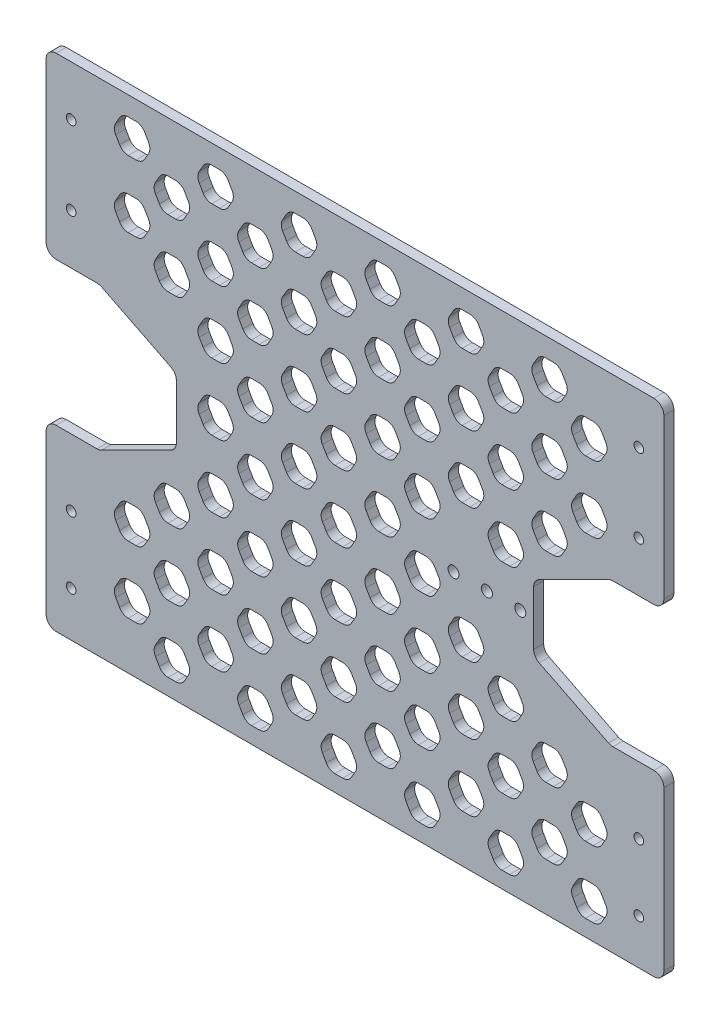
SolidWorks part; units mm, degrees
material "轻木"
ref_plane "前视基准面" through (0, 0, 0) normal (0, 0, 1) x (1, 0, 0)
ref_plane "上视基准面" through (0, 0, 0) normal (0, 1, 0) x (1, 0, 0)
ref_plane "右视基准面" through (0, 0, 0) normal (1, 0, 0) x (0, 0, -1)
other "Configuration Table"
sketch "草图2" plane through (0, 0, 0) normal (0, 0, 1) x (1, 0, 0)
  line L0 (-15, 79) -> (-15, 17.5) construction
  line L1 (-155.6985, 79) -> (0, 79) construction
  line L2 (-15, 285) -> (-15, -285) construction
  line L3 (-15, 17.5) -> (0, 17.5) construction
  line L4 (0, 285) -> (0, -285) construction
  line L5 (0, 17.5) -> (20, 7.5) construction
  line L6 (155, 7.5) -> (0, 7.5) construction
  line L8 (155, -7.5) -> (0, -7.5) construction
  line L9 (20, -7.5) -> (135, -7.5) construction
  line L11 (135, 7.5) -> (155, 17.5) construction
  line L12 (155, 285) -> (155, -285) construction
  line L13 (155, 17.5) -> (170, 17.5) construction
  line L14 (170, 285) -> (170, -285) construction
  line L15 (170, 17.5) -> (170, 79) construction
  line L16 (170, 79) -> (-15, 79) construction
  line L17 (20, 7.5) -> (20, -7.5) construction
  line L18 (137.7639, 8.882) -> (153.9443, 16.9721) construction
  line L19 (1.0557, 16.9721) -> (17.2361, 8.882) construction
  line L20 (-1000, 0) -> (49000, 0) construction
  line L21 (135, 7.5) -> (135, -7.5) construction
  line L22 (131, 9.9721) -> (131, -3.5) construction
  line L23 (24, -3.5) -> (131, -3.5) construction
  line L24 (24, 9.9721) -> (24, -3.5) construction
  line L25 (0.9443, 21.5) -> (24, 9.9721) construction
  line L26 (-11, 21.5) -> (0.9443, 21.5) construction
  line L27 (-11, 75) -> (-11, 21.5) construction
  line L28 (166, 75) -> (-11, 75) construction
  line L29 (166, 21.5) -> (166, 75) construction
  line L30 (154.0557, 21.5) -> (166, 21.5) construction
  line L31 (131, 9.9721) -> (154.0557, 21.5) construction
  line L32 (131, -9.9721) -> (154.0557, -21.5) construction
  line L33 (154.0557, -21.5) -> (166, -21.5) construction
  line L34 (166, -21.5) -> (166, -75) construction
  line L35 (166, -75) -> (-11, -75) construction
  line L36 (-11, -75) -> (-11, -21.5) construction
  line L37 (-11, -21.5) -> (0.9443, -21.5) construction
  line L38 (0.9443, -21.5) -> (24, -9.9721) construction
  line L39 (24, -9.9721) -> (24, 3.5) construction
  line L40 (24, 3.5) -> (131, 3.5) construction
  line L41 (131, -9.9721) -> (131, 3.5) construction
  line L42 (170, 75) -> (-15, 75)
  line L43 (-15, 75) -> (-15, 21.5)
  line L44 (-15, 21.5) -> (0.9443, 21.5)
  line L45 (0.9443, 21.5) -> (24, 9.9721)
  line L46 (24, 9.9721) -> (24, -9.9721)
  line L47 (24, -9.9721) -> (0.9443, -21.5)
  line L48 (0.9443, -21.5) -> (-15, -21.5)
  line L49 (-15, -21.5) -> (-15, -75)
  line L50 (-15, -75) -> (170, -75)
  line L51 (170, -75) -> (170, -21.5)
  line L52 (170, -21.5) -> (154.0557, -21.5)
  line L53 (154.0557, -21.5) -> (131, -9.9721)
  line L54 (131, -9.9721) -> (131, 9.9721)
  line L55 (131, 9.9721) -> (154.0557, 21.5)
  line L56 (154.0557, 21.5) -> (170, 21.5)
  line L57 (170, 21.5) -> (170, 75)
  dimension "D1" = 4
extrude "凸台-拉伸1" add sketch "草图2" along normal blind 3
fillet "圆角1" radius 3 16 edges at (131, 9.9721, 1.5) (131, -9.9721, 1.5) (154.0557, -21.5, 1.5) (170, -21.5, 1.5) (170, -75, 1.5) (-15, -75, 1.5) (-15, -21.5, 1.5) (0.9443, -21.5, 1.5) (24, -9.9721, 1.5) (24, 9.9721, 1.5) (0.9443, 21.5, 1.5) (-15, 21.5, 1.5) (-15, 75, 1.5) (154.0557, 21.5, 1.5) (170, 21.5, 1.5) (170, 75, 1.5)
sketch "草图3" plane through (0, 0, 3) normal (0, 0, 1) x (1, 0, 0)
  line L0 (-7.5, 86.2076) -> (-7.5, -86.6674) construction
  line L1 (162.5, 91.5716) -> (162.5, -92.3379) construction
  line L2 (170, 24.5) -> (170, 72) construction
  line L5 (-15, 72) -> (-15, 24.5) construction
  line L6 (-12, 21.5) -> (0.2361, 21.5) construction
  line L7 (167, 75) -> (-12, 75) construction
  line L8 (154.7639, 21.5) -> (167, 21.5) construction
  line L9 (167, -21.5) -> (154.7639, -21.5) construction
  line L11 (0.2361, -21.5) -> (-12, -21.5) construction
  circle A0 centre (-7.5, 60) radius 1.45
  circle A1 centre (162.5, 60) radius 1.45
  circle A2 centre (-7.5, -61.5) radius 1.45
  circle A3 centre (162.5, -61.5) radius 1.45
  circle A4 centre (-7.5, 36.5) radius 1.45
  circle A5 centre (162.5, 36.5) radius 1.45
  circle A6 centre (162.5, -41.5) radius 1.45
  circle A7 centre (-7.5, -41.5) radius 1.45
  dimension "D3" = 2.9
  dimension "D4" = 15
  dimension "D5" = 15
  dimension "D6" = 15
  dimension "D7" = 15
  dimension "D8" = 20
  dimension "D9" = 20
  dimension "D11" = 20
  dimension "D1" = 7.5
  dimension "D2" = 7.5
  dimension "D10" = 20
extrude "切除-拉伸1" cut sketch "草图3" against normal blind 10
sketch "草图4" plane through (0, 0, 0) normal (0, 0, -1) x (-1, 0, 0)
  circle A0 centre (-127, 0) radius 1.65 construction
  circle A1 centre (-127, 0) radius 1.65
  circle A2 centre (-107, 0) radius 1.65 construction
  circle A3 centre (-117, 0) radius 1.65 construction
  circle A4 centre (-107, 0) radius 1.65
  circle A5 centre (-117, 0) radius 1.65
extrude "切除-拉伸2" cut sketch "草图4" against normal through all
sketch "草图5" plane through (0, 0, 3) normal (0, 0, 1) x (1, 0, 0)
  line L1 (41.534, 64.2649) -> (38.6472, 69.2649)
  line L2 (16.534, 64.2649) -> (13.6472, 69.2649)
  line L3 (13.6472, 69.2649) -> (7.8737, 69.2649)
  line L4 (7.8737, 69.2649) -> (4.987, 64.2649)
  line L5 (4.987, 64.2649) -> (7.8737, 59.2649)
  line L6 (7.8737, 59.2649) -> (13.6472, 59.2649)
  line L7 (13.6472, 59.2649) -> (16.534, 64.2649)
  line L8 (28.4406, 54.8878) -> (25.5539, 59.8878)
  line L9 (25.5539, 59.8878) -> (19.7804, 59.8878)
  line L10 (19.7804, 59.8878) -> (16.8936, 54.8878)
  line L11 (16.8936, 54.8878) -> (19.7804, 49.8878)
  line L12 (19.7804, 49.8878) -> (25.5539, 49.8878)
  line L13 (25.5539, 49.8878) -> (28.4406, 54.8878)
  line L14 (38.6472, 69.2649) -> (32.8737, 69.2649)
  line L15 (32.8737, 69.2649) -> (29.987, 64.2649)
  line L16 (29.987, 64.2649) -> (32.8737, 59.2649)
  line L17 (32.8737, 59.2649) -> (38.6472, 59.2649)
  line L18 (38.6472, 59.2649) -> (41.534, 64.2649)
  line L19 (53.4406, 54.8878) -> (50.5539, 59.8878)
  line L20 (50.5539, 59.8878) -> (44.7804, 59.8878)
  line L21 (44.7804, 59.8878) -> (41.8936, 54.8878)
  line L22 (41.8936, 54.8878) -> (44.7804, 49.8878)
  line L23 (44.7804, 49.8878) -> (50.5539, 49.8878)
  line L24 (50.5539, 49.8878) -> (53.4406, 54.8878)
  line L25 (66.534, 64.2649) -> (63.6472, 69.2649)
  line L26 (63.6472, 69.2649) -> (57.8737, 69.2649)
  line L27 (57.8737, 69.2649) -> (54.987, 64.2649)
  line L28 (54.987, 64.2649) -> (57.8737, 59.2649)
  line L29 (57.8737, 59.2649) -> (63.6472, 59.2649)
  line L30 (63.6472, 59.2649) -> (66.534, 64.2649)
  line L31 (78.4406, 54.8878) -> (75.5539, 59.8878)
  line L32 (75.5539, 59.8878) -> (69.7804, 59.8878)
  line L33 (69.7804, 59.8878) -> (66.8936, 54.8878)
  line L34 (66.8936, 54.8878) -> (69.7804, 49.8878)
  line L35 (69.7804, 49.8878) -> (75.5539, 49.8878)
  line L36 (75.5539, 49.8878) -> (78.4406, 54.8878)
  line L37 (91.534, 64.2649) -> (88.6472, 69.2649)
  line L38 (88.6472, 69.2649) -> (82.8737, 69.2649)
  line L39 (82.8737, 69.2649) -> (79.987, 64.2649)
  line L40 (79.987, 64.2649) -> (82.8737, 59.2649)
  line L41 (82.8737, 59.2649) -> (88.6472, 59.2649)
  line L42 (88.6472, 59.2649) -> (91.534, 64.2649)
  line L43 (103.4406, 54.8878) -> (100.5539, 59.8878)
  line L44 (100.5539, 59.8878) -> (94.7804, 59.8878)
  line L45 (94.7804, 59.8878) -> (91.8936, 54.8878)
  line L46 (91.8936, 54.8878) -> (94.7804, 49.8878)
  line L47 (94.7804, 49.8878) -> (100.5539, 49.8878)
  line L48 (100.5539, 49.8878) -> (103.4406, 54.8878)
  line L49 (116.534, 64.2649) -> (113.6472, 69.2649)
  line L50 (113.6472, 69.2649) -> (107.8737, 69.2649)
  line L51 (107.8737, 69.2649) -> (104.987, 64.2649)
  line L52 (104.987, 64.2649) -> (107.8737, 59.2649)
  line L53 (107.8737, 59.2649) -> (113.6472, 59.2649)
  line L54 (113.6472, 59.2649) -> (116.534, 64.2649)
  line L55 (128.4406, 54.8878) -> (125.5539, 59.8878)
  line L56 (125.5539, 59.8878) -> (119.7804, 59.8878)
  line L57 (119.7804, 59.8878) -> (116.8936, 54.8878)
  line L58 (116.8936, 54.8878) -> (119.7804, 49.8878)
  line L59 (119.7804, 49.8878) -> (125.5539, 49.8878)
  line L60 (125.5539, 49.8878) -> (128.4406, 54.8878)
  line L61 (141.534, 64.2649) -> (138.6472, 69.2649)
  line L62 (138.6472, 69.2649) -> (132.8737, 69.2649)
  line L63 (132.8737, 69.2649) -> (129.987, 64.2649)
  line L64 (129.987, 64.2649) -> (132.8737, 59.2649)
  line L65 (132.8737, 59.2649) -> (138.6472, 59.2649)
  line L66 (138.6472, 59.2649) -> (141.534, 64.2649)
  line L67 (153.4406, 54.8878) -> (150.5539, 59.8878)
  line L68 (150.5539, 59.8878) -> (144.7804, 59.8878)
  line L69 (144.7804, 59.8878) -> (141.8936, 54.8878)
  line L70 (141.8936, 54.8878) -> (144.7804, 49.8878)
  line L71 (144.7804, 49.8878) -> (150.5539, 49.8878)
  line L72 (150.5539, 49.8878) -> (153.4406, 54.8878)
  line L73 (41.534, 44.2649) -> (38.6472, 49.2649)
  line L74 (38.6472, 49.2649) -> (32.8737, 49.2649)
  line L75 (32.8737, 49.2649) -> (29.987, 44.2649)
  line L76 (29.987, 44.2649) -> (32.8737, 39.2649)
  line L77 (32.8737, 39.2649) -> (38.6472, 39.2649)
  line L78 (38.6472, 39.2649) -> (41.534, 44.2649)
  line L79 (53.4406, 34.8878) -> (50.5539, 39.8878)
  line L80 (50.5539, 39.8878) -> (44.7804, 39.8878)
  line L81 (44.7804, 39.8878) -> (41.8936, 34.8878)
  line L82 (41.8936, 34.8878) -> (44.7804, 29.8878)
  line L83 (44.7804, 29.8878) -> (50.5539, 29.8878)
  line L84 (50.5539, 29.8878) -> (53.4406, 34.8878)
  line L85 (66.534, 44.2649) -> (63.6472, 49.2649)
  line L86 (63.6472, 49.2649) -> (57.8737, 49.2649)
  line L87 (57.8737, 49.2649) -> (54.987, 44.2649)
  line L88 (54.987, 44.2649) -> (57.8737, 39.2649)
  line L89 (57.8737, 39.2649) -> (63.6472, 39.2649)
  line L90 (63.6472, 39.2649) -> (66.534, 44.2649)
  line L91 (78.4406, 34.8878) -> (75.5539, 39.8878)
  line L92 (75.5539, 39.8878) -> (69.7804, 39.8878)
  line L93 (69.7804, 39.8878) -> (66.8936, 34.8878)
  line L94 (66.8936, 34.8878) -> (69.7804, 29.8878)
  line L95 (69.7804, 29.8878) -> (75.5539, 29.8878)
  line L96 (75.5539, 29.8878) -> (78.4406, 34.8878)
  line L97 (91.534, 44.2649) -> (88.6472, 49.2649)
  line L98 (88.6472, 49.2649) -> (82.8737, 49.2649)
  line L99 (82.8737, 49.2649) -> (79.987, 44.2649)
  line L100 (79.987, 44.2649) -> (82.8737, 39.2649)
  line L101 (82.8737, 39.2649) -> (88.6472, 39.2649)
  line L102 (88.6472, 39.2649) -> (91.534, 44.2649)
  line L103 (103.4406, 34.8878) -> (100.5539, 39.8878)
  line L104 (100.5539, 39.8878) -> (94.7804, 39.8878)
  line L105 (94.7804, 39.8878) -> (91.8936, 34.8878)
  line L106 (91.8936, 34.8878) -> (94.7804, 29.8878)
  line L107 (94.7804, 29.8878) -> (100.5539, 29.8878)
  line L108 (100.5539, 29.8878) -> (103.4406, 34.8878)
  line L109 (116.534, 44.2649) -> (113.6472, 49.2649)
  line L110 (113.6472, 49.2649) -> (107.8737, 49.2649)
  line L111 (107.8737, 49.2649) -> (104.987, 44.2649)
  line L112 (104.987, 44.2649) -> (107.8737, 39.2649)
  line L113 (107.8737, 39.2649) -> (113.6472, 39.2649)
  line L114 (113.6472, 39.2649) -> (116.534, 44.2649)
  line L115 (128.4406, 34.8878) -> (125.5539, 39.8878)
  line L116 (125.5539, 39.8878) -> (119.7804, 39.8878)
  line L117 (119.7804, 39.8878) -> (116.8936, 34.8878)
  line L118 (116.8936, 34.8878) -> (119.7804, 29.8878)
  line L119 (119.7804, 29.8878) -> (125.5539, 29.8878)
  line L120 (125.5539, 29.8878) -> (128.4406, 34.8878)
  line L121 (141.534, 44.2649) -> (138.6472, 49.2649)
  line L122 (138.6472, 49.2649) -> (132.8737, 49.2649)
  line L123 (132.8737, 49.2649) -> (129.987, 44.2649)
  line L124 (129.987, 44.2649) -> (132.8737, 39.2649)
  line L125 (132.8737, 39.2649) -> (138.6472, 39.2649)
  line L126 (138.6472, 39.2649) -> (141.534, 44.2649)
  line L127 (153.4406, 34.8878) -> (150.5539, 39.8878)
  line L128 (150.5539, 39.8878) -> (144.7804, 39.8878)
  line L129 (144.7804, 39.8878) -> (141.8936, 34.8878)
  line L130 (141.8936, 34.8878) -> (144.7804, 29.8878)
  line L131 (144.7804, 29.8878) -> (150.5539, 29.8878)
  line L132 (150.5539, 29.8878) -> (153.4406, 34.8878)
  line L133 (41.534, 24.2649) -> (38.6472, 29.2649)
  line L134 (38.6472, 29.2649) -> (32.8737, 29.2649)
  line L135 (32.8737, 29.2649) -> (29.987, 24.2649)
  line L136 (29.987, 24.2649) -> (32.8737, 19.2649)
  line L137 (32.8737, 19.2649) -> (38.6472, 19.2649)
  line L138 (38.6472, 19.2649) -> (41.534, 24.2649)
  line L139 (53.4406, 14.8878) -> (50.5539, 19.8878)
  line L140 (50.5539, 19.8878) -> (44.7804, 19.8878)
  line L141 (44.7804, 19.8878) -> (41.8936, 14.8878)
  line L142 (41.8936, 14.8878) -> (44.7804, 9.8878)
  line L143 (44.7804, 9.8878) -> (50.5539, 9.8878)
  line L144 (50.5539, 9.8878) -> (53.4406, 14.8878)
  line L145 (66.534, 24.2649) -> (63.6472, 29.2649)
  line L146 (63.6472, 29.2649) -> (57.8737, 29.2649)
  line L147 (57.8737, 29.2649) -> (54.987, 24.2649)
  line L148 (54.987, 24.2649) -> (57.8737, 19.2649)
  line L149 (57.8737, 19.2649) -> (63.6472, 19.2649)
  line L150 (63.6472, 19.2649) -> (66.534, 24.2649)
  line L151 (78.4406, 14.8878) -> (75.5539, 19.8878)
  line L152 (75.5539, 19.8878) -> (69.7804, 19.8878)
  line L153 (69.7804, 19.8878) -> (66.8936, 14.8878)
  line L154 (66.8936, 14.8878) -> (69.7804, 9.8878)
  line L155 (69.7804, 9.8878) -> (75.5539, 9.8878)
  line L156 (75.5539, 9.8878) -> (78.4406, 14.8878)
  line L157 (91.534, 24.2649) -> (88.6472, 29.2649)
  line L158 (88.6472, 29.2649) -> (82.8737, 29.2649)
  line L159 (82.8737, 29.2649) -> (79.987, 24.2649)
  line L160 (79.987, 24.2649) -> (82.8737, 19.2649)
  line L161 (82.8737, 19.2649) -> (88.6472, 19.2649)
  line L162 (88.6472, 19.2649) -> (91.534, 24.2649)
  line L163 (103.4406, 14.8878) -> (100.5539, 19.8878)
  line L164 (100.5539, 19.8878) -> (94.7804, 19.8878)
  line L165 (94.7804, 19.8878) -> (91.8936, 14.8878)
  line L166 (91.8936, 14.8878) -> (94.7804, 9.8878)
  line L167 (94.7804, 9.8878) -> (100.5539, 9.8878)
  line L168 (100.5539, 9.8878) -> (103.4406, 14.8878)
  line L169 (116.534, 24.2649) -> (113.6472, 29.2649)
  line L170 (113.6472, 29.2649) -> (107.8737, 29.2649)
  line L171 (107.8737, 29.2649) -> (104.987, 24.2649)
  line L172 (104.987, 24.2649) -> (107.8737, 19.2649)
  line L173 (107.8737, 19.2649) -> (113.6472, 19.2649)
  line L174 (113.6472, 19.2649) -> (116.534, 24.2649)
  line L175 (128.4406, 14.8878) -> (125.5539, 19.8878)
  line L176 (125.5539, 19.8878) -> (119.7804, 19.8878)
  line L177 (119.7804, 19.8878) -> (116.8936, 14.8878)
  line L178 (116.8936, 14.8878) -> (119.7804, 9.8878)
  line L179 (119.7804, 9.8878) -> (125.5539, 9.8878)
  line L180 (125.5539, 9.8878) -> (128.4406, 14.8878)
  line L181 (141.534, 24.2649) -> (138.6472, 29.2649)
  line L182 (138.6472, 29.2649) -> (132.8737, 29.2649)
  line L183 (132.8737, 29.2649) -> (129.987, 24.2649)
  line L184 (129.987, 24.2649) -> (132.8737, 19.2649)
  line L185 (132.8737, 19.2649) -> (138.6472, 19.2649)
  line L186 (138.6472, 19.2649) -> (141.534, 24.2649)
  line L193 (41.534, 4.2649) -> (38.6472, 9.2649)
  line L194 (38.6472, 9.2649) -> (32.8737, 9.2649)
  line L195 (32.8737, 9.2649) -> (29.987, 4.2649)
  line L196 (29.987, 4.2649) -> (32.8737, -0.7351)
  line L197 (32.8737, -0.7351) -> (38.6472, -0.7351)
  line L198 (38.6472, -0.7351) -> (41.534, 4.2649)
  line L199 (53.4406, -5.1122) -> (50.5539, -0.1122)
  line L200 (50.5539, -0.1122) -> (44.7804, -0.1122)
  line L201 (44.7804, -0.1122) -> (41.8936, -5.1122)
  line L202 (41.8936, -5.1122) -> (44.7804, -10.1122)
  line L203 (44.7804, -10.1122) -> (50.5539, -10.1122)
  line L204 (50.5539, -10.1122) -> (53.4406, -5.1122)
  line L205 (66.534, 4.2649) -> (63.6472, 9.2649)
  line L206 (63.6472, 9.2649) -> (57.8737, 9.2649)
  line L207 (57.8737, 9.2649) -> (54.987, 4.2649)
  line L208 (54.987, 4.2649) -> (57.8737, -0.7351)
  line L209 (57.8737, -0.7351) -> (63.6472, -0.7351)
  line L210 (63.6472, -0.7351) -> (66.534, 4.2649)
  line L211 (78.4406, -5.1122) -> (75.5539, -0.1122)
  line L212 (75.5539, -0.1122) -> (69.7804, -0.1122)
  line L213 (69.7804, -0.1122) -> (66.8936, -5.1122)
  line L214 (66.8936, -5.1122) -> (69.7804, -10.1122)
  line L215 (69.7804, -10.1122) -> (75.5539, -10.1122)
  line L216 (75.5539, -10.1122) -> (78.4406, -5.1122)
  line L217 (91.534, 4.2649) -> (88.6472, 9.2649)
  line L218 (88.6472, 9.2649) -> (82.8737, 9.2649)
  line L219 (82.8737, 9.2649) -> (79.987, 4.2649)
  line L220 (79.987, 4.2649) -> (82.8737, -0.7351)
  line L221 (82.8737, -0.7351) -> (88.6472, -0.7351)
  line L222 (88.6472, -0.7351) -> (91.534, 4.2649)
  line L223 (103.4406, -5.1122) -> (100.5539, -0.1122)
  line L224 (100.5539, -0.1122) -> (94.7804, -0.1122)
  line L225 (94.7804, -0.1122) -> (91.8936, -5.1122)
  line L226 (91.8936, -5.1122) -> (94.7804, -10.1122)
  line L227 (94.7804, -10.1122) -> (100.5539, -10.1122)
  line L228 (100.5539, -10.1122) -> (103.4406, -5.1122)
  line L253 (41.534, -15.7351) -> (38.6472, -10.7351)
  line L254 (38.6472, -10.7351) -> (32.8737, -10.7351)
  line L255 (32.8737, -10.7351) -> (29.987, -15.7351)
  line L256 (29.987, -15.7351) -> (32.8737, -20.7351)
  line L257 (32.8737, -20.7351) -> (38.6472, -20.7351)
  line L258 (38.6472, -20.7351) -> (41.534, -15.7351)
  line L259 (53.4406, -25.1122) -> (50.5539, -20.1122)
  line L260 (50.5539, -20.1122) -> (44.7804, -20.1122)
  line L261 (44.7804, -20.1122) -> (41.8936, -25.1122)
  line L262 (41.8936, -25.1122) -> (44.7804, -30.1122)
  line L263 (44.7804, -30.1122) -> (50.5539, -30.1122)
  line L264 (50.5539, -30.1122) -> (53.4406, -25.1122)
  line L265 (66.534, -15.7351) -> (63.6472, -10.7351)
  line L266 (63.6472, -10.7351) -> (57.8737, -10.7351)
  line L267 (57.8737, -10.7351) -> (54.987, -15.7351)
  line L268 (54.987, -15.7351) -> (57.8737, -20.7351)
  line L269 (57.8737, -20.7351) -> (63.6472, -20.7351)
  line L270 (63.6472, -20.7351) -> (66.534, -15.7351)
  line L271 (78.4406, -25.1122) -> (75.5539, -20.1122)
  line L272 (75.5539, -20.1122) -> (69.7804, -20.1122)
  line L273 (69.7804, -20.1122) -> (66.8936, -25.1122)
  line L274 (66.8936, -25.1122) -> (69.7804, -30.1122)
  line L275 (69.7804, -30.1122) -> (75.5539, -30.1122)
  line L276 (75.5539, -30.1122) -> (78.4406, -25.1122)
  line L277 (91.534, -15.7351) -> (88.6472, -10.7351)
  line L278 (88.6472, -10.7351) -> (82.8737, -10.7351)
  line L279 (82.8737, -10.7351) -> (79.987, -15.7351)
  line L280 (79.987, -15.7351) -> (82.8737, -20.7351)
  line L281 (82.8737, -20.7351) -> (88.6472, -20.7351)
  line L282 (88.6472, -20.7351) -> (91.534, -15.7351)
  line L283 (103.4406, -25.1122) -> (100.5539, -20.1122)
  line L284 (100.5539, -20.1122) -> (94.7804, -20.1122)
  line L285 (94.7804, -20.1122) -> (91.8936, -25.1122)
  line L286 (91.8936, -25.1122) -> (94.7804, -30.1122)
  line L287 (94.7804, -30.1122) -> (100.5539, -30.1122)
  line L288 (100.5539, -30.1122) -> (103.4406, -25.1122)
  line L289 (116.534, -15.7351) -> (113.6472, -10.7351)
  line L290 (113.6472, -10.7351) -> (107.8737, -10.7351)
  line L291 (107.8737, -10.7351) -> (104.987, -15.7351)
  line L292 (104.987, -15.7351) -> (107.8737, -20.7351)
  line L293 (107.8737, -20.7351) -> (113.6472, -20.7351)
  line L294 (113.6472, -20.7351) -> (116.534, -15.7351)
  line L295 (128.4406, -25.1122) -> (125.5539, -20.1122)
  line L296 (125.5539, -20.1122) -> (119.7804, -20.1122)
  line L297 (119.7804, -20.1122) -> (116.8936, -25.1122)
  line L298 (116.8936, -25.1122) -> (119.7804, -30.1122)
  line L299 (119.7804, -30.1122) -> (125.5539, -30.1122)
  line L300 (125.5539, -30.1122) -> (128.4406, -25.1122)
  line L313 (41.534, -35.7351) -> (38.6472, -30.7351)
  line L314 (38.6472, -30.7351) -> (32.8737, -30.7351)
  line L315 (32.8737, -30.7351) -> (29.987, -35.7351)
  line L316 (29.987, -35.7351) -> (32.8737, -40.7351)
  line L317 (32.8737, -40.7351) -> (38.6472, -40.7351)
  line L318 (38.6472, -40.7351) -> (41.534, -35.7351)
  line L319 (53.4406, -45.1122) -> (50.5539, -40.1122)
  line L320 (50.5539, -40.1122) -> (44.7804, -40.1122)
  line L321 (44.7804, -40.1122) -> (41.8936, -45.1122)
  line L322 (41.8936, -45.1122) -> (44.7804, -50.1122)
  line L323 (44.7804, -50.1122) -> (50.5539, -50.1122)
  line L324 (50.5539, -50.1122) -> (53.4406, -45.1122)
  line L325 (66.534, -35.7351) -> (63.6472, -30.7351)
  line L326 (63.6472, -30.7351) -> (57.8737, -30.7351)
  line L327 (57.8737, -30.7351) -> (54.987, -35.7351)
  line L328 (54.987, -35.7351) -> (57.8737, -40.7351)
  line L329 (57.8737, -40.7351) -> (63.6472, -40.7351)
  line L330 (63.6472, -40.7351) -> (66.534, -35.7351)
  line L331 (78.4406, -45.1122) -> (75.5539, -40.1122)
  line L332 (75.5539, -40.1122) -> (69.7804, -40.1122)
  line L333 (69.7804, -40.1122) -> (66.8936, -45.1122)
  line L334 (66.8936, -45.1122) -> (69.7804, -50.1122)
  line L335 (69.7804, -50.1122) -> (75.5539, -50.1122)
  line L336 (75.5539, -50.1122) -> (78.4406, -45.1122)
  line L337 (91.534, -35.7351) -> (88.6472, -30.7351)
  line L338 (88.6472, -30.7351) -> (82.8737, -30.7351)
  line L339 (82.8737, -30.7351) -> (79.987, -35.7351)
  line L340 (79.987, -35.7351) -> (82.8737, -40.7351)
  line L341 (82.8737, -40.7351) -> (88.6472, -40.7351)
  line L342 (88.6472, -40.7351) -> (91.534, -35.7351)
  line L343 (103.4406, -45.1122) -> (100.5539, -40.1122)
  line L344 (100.5539, -40.1122) -> (94.7804, -40.1122)
  line L345 (94.7804, -40.1122) -> (91.8936, -45.1122)
  line L346 (91.8936, -45.1122) -> (94.7804, -50.1122)
  line L347 (94.7804, -50.1122) -> (100.5539, -50.1122)
  line L348 (100.5539, -50.1122) -> (103.4406, -45.1122)
  line L349 (116.534, -35.7351) -> (113.6472, -30.7351)
  line L350 (113.6472, -30.7351) -> (107.8737, -30.7351)
  line L351 (107.8737, -30.7351) -> (104.987, -35.7351)
  line L352 (104.987, -35.7351) -> (107.8737, -40.7351)
  line L353 (107.8737, -40.7351) -> (113.6472, -40.7351)
  line L354 (113.6472, -40.7351) -> (116.534, -35.7351)
  line L355 (128.4406, -45.1122) -> (125.5539, -40.1122)
  line L356 (125.5539, -40.1122) -> (119.7804, -40.1122)
  line L357 (119.7804, -40.1122) -> (116.8936, -45.1122)
  line L358 (116.8936, -45.1122) -> (119.7804, -50.1122)
  line L359 (119.7804, -50.1122) -> (125.5539, -50.1122)
  line L360 (125.5539, -50.1122) -> (128.4406, -45.1122)
  line L361 (141.534, -35.7351) -> (138.6472, -30.7351)
  line L362 (138.6472, -30.7351) -> (132.8737, -30.7351)
  line L363 (132.8737, -30.7351) -> (129.987, -35.7351)
  line L364 (129.987, -35.7351) -> (132.8737, -40.7351)
  line L365 (132.8737, -40.7351) -> (138.6472, -40.7351)
  line L366 (138.6472, -40.7351) -> (141.534, -35.7351)
  line L367 (153.4406, -45.1122) -> (150.5539, -40.1122)
  line L368 (150.5539, -40.1122) -> (144.7804, -40.1122)
  line L369 (144.7804, -40.1122) -> (141.8936, -45.1122)
  line L370 (141.8936, -45.1122) -> (144.7804, -50.1122)
  line L371 (144.7804, -50.1122) -> (150.5539, -50.1122)
  line L372 (150.5539, -50.1122) -> (153.4406, -45.1122)
  line L373 (41.534, -55.7351) -> (38.6472, -50.7351)
  line L374 (38.6472, -50.7351) -> (32.8737, -50.7351)
  line L375 (32.8737, -50.7351) -> (29.987, -55.7351)
  line L376 (29.987, -55.7351) -> (32.8737, -60.7351)
  line L377 (32.8737, -60.7351) -> (38.6472, -60.7351)
  line L378 (38.6472, -60.7351) -> (41.534, -55.7351)
  line L379 (53.4406, -65.1122) -> (50.5539, -60.1122)
  line L380 (50.5539, -60.1122) -> (44.7804, -60.1122)
  line L381 (44.7804, -60.1122) -> (41.8936, -65.1122)
  line L382 (41.8936, -65.1122) -> (44.7804, -70.1122)
  line L383 (44.7804, -70.1122) -> (50.5539, -70.1122)
  line L384 (50.5539, -70.1122) -> (53.4406, -65.1122)
  line L385 (66.534, -55.7351) -> (63.6472, -50.7351)
  line L386 (63.6472, -50.7351) -> (57.8737, -50.7351)
  line L387 (57.8737, -50.7351) -> (54.987, -55.7351)
  line L388 (54.987, -55.7351) -> (57.8737, -60.7351)
  line L389 (57.8737, -60.7351) -> (63.6472, -60.7351)
  line L390 (63.6472, -60.7351) -> (66.534, -55.7351)
  line L391 (78.4406, -65.1122) -> (75.5539, -60.1122)
  line L392 (75.5539, -60.1122) -> (69.7804, -60.1122)
  line L393 (69.7804, -60.1122) -> (66.8936, -65.1122)
  line L394 (66.8936, -65.1122) -> (69.7804, -70.1122)
  line L395 (69.7804, -70.1122) -> (75.5539, -70.1122)
  line L396 (75.5539, -70.1122) -> (78.4406, -65.1122)
  line L397 (91.534, -55.7351) -> (88.6472, -50.7351)
  line L398 (88.6472, -50.7351) -> (82.8737, -50.7351)
  line L399 (82.8737, -50.7351) -> (79.987, -55.7351)
  line L400 (79.987, -55.7351) -> (82.8737, -60.7351)
  line L401 (82.8737, -60.7351) -> (88.6472, -60.7351)
  line L402 (88.6472, -60.7351) -> (91.534, -55.7351)
  line L403 (103.4406, -65.1122) -> (100.5539, -60.1122)
  line L404 (100.5539, -60.1122) -> (94.7804, -60.1122)
  line L405 (94.7804, -60.1122) -> (91.8936, -65.1122)
  line L406 (91.8936, -65.1122) -> (94.7804, -70.1122)
  line L407 (94.7804, -70.1122) -> (100.5539, -70.1122)
  line L408 (100.5539, -70.1122) -> (103.4406, -65.1122)
  line L409 (116.534, -55.7351) -> (113.6472, -50.7351)
  line L410 (113.6472, -50.7351) -> (107.8737, -50.7351)
  line L411 (107.8737, -50.7351) -> (104.987, -55.7351)
  line L412 (104.987, -55.7351) -> (107.8737, -60.7351)
  line L413 (107.8737, -60.7351) -> (113.6472, -60.7351)
  line L414 (113.6472, -60.7351) -> (116.534, -55.7351)
  line L415 (128.4406, -65.1122) -> (125.5539, -60.1122)
  line L416 (125.5539, -60.1122) -> (119.7804, -60.1122)
  line L417 (119.7804, -60.1122) -> (116.8936, -65.1122)
  line L418 (116.8936, -65.1122) -> (119.7804, -70.1122)
  line L419 (119.7804, -70.1122) -> (125.5539, -70.1122)
  line L420 (125.5539, -70.1122) -> (128.4406, -65.1122)
  line L421 (141.534, -55.7351) -> (138.6472, -50.7351)
  line L422 (138.6472, -50.7351) -> (132.8737, -50.7351)
  line L423 (132.8737, -50.7351) -> (129.987, -55.7351)
  line L424 (129.987, -55.7351) -> (132.8737, -60.7351)
  line L425 (132.8737, -60.7351) -> (138.6472, -60.7351)
  line L426 (138.6472, -60.7351) -> (141.534, -55.7351)
  line L427 (153.4406, -65.1122) -> (150.5539, -60.1122)
  line L428 (150.5539, -60.1122) -> (144.7804, -60.1122)
  line L429 (144.7804, -60.1122) -> (141.8936, -65.1122)
  line L430 (141.8936, -65.1122) -> (144.7804, -70.1122)
  line L431 (144.7804, -70.1122) -> (150.5539, -70.1122)
  line L432 (150.5539, -70.1122) -> (153.4406, -65.1122)
  line L433 (16.534, 44.2649) -> (13.6472, 49.2649)
  line L434 (13.6472, 49.2649) -> (7.8737, 49.2649)
  line L435 (7.8737, 49.2649) -> (4.987, 44.2649)
  line L436 (4.987, 44.2649) -> (7.8737, 39.2649)
  line L437 (7.8737, 39.2649) -> (13.6472, 39.2649)
  line L438 (13.6472, 39.2649) -> (16.534, 44.2649)
  line L439 (28.4406, 34.8878) -> (25.5539, 39.8878)
  line L440 (25.5539, 39.8878) -> (19.7804, 39.8878)
  line L441 (19.7804, 39.8878) -> (16.8936, 34.8878)
  line L442 (16.8936, 34.8878) -> (19.7804, 29.8878)
  line L443 (19.7804, 29.8878) -> (25.5539, 29.8878)
  line L444 (25.5539, 29.8878) -> (28.4406, 34.8878)
  line L475 (28.4406, -25.1122) -> (25.5539, -20.1122)
  line L476 (25.5539, -20.1122) -> (19.7804, -20.1122)
  line L477 (19.7804, -20.1122) -> (16.8936, -25.1122)
  line L478 (16.8936, -25.1122) -> (19.7804, -30.1122)
  line L479 (19.7804, -30.1122) -> (25.5539, -30.1122)
  line L480 (25.5539, -30.1122) -> (28.4406, -25.1122)
  line L481 (16.534, -35.7351) -> (13.6472, -30.7351)
  line L482 (13.6472, -30.7351) -> (7.8737, -30.7351)
  line L483 (7.8737, -30.7351) -> (4.987, -35.7351)
  line L484 (4.987, -35.7351) -> (7.8737, -40.7351)
  line L485 (7.8737, -40.7351) -> (13.6472, -40.7351)
  line L486 (13.6472, -40.7351) -> (16.534, -35.7351)
  line L487 (28.4406, -45.1122) -> (25.5539, -40.1122)
  line L488 (25.5539, -40.1122) -> (19.7804, -40.1122)
  line L489 (19.7804, -40.1122) -> (16.8936, -45.1122)
  line L490 (16.8936, -45.1122) -> (19.7804, -50.1122)
  line L491 (19.7804, -50.1122) -> (25.5539, -50.1122)
  line L492 (25.5539, -50.1122) -> (28.4406, -45.1122)
  line L493 (16.534, -55.7351) -> (13.6472, -50.7351)
  line L494 (13.6472, -50.7351) -> (7.8737, -50.7351)
  line L495 (7.8737, -50.7351) -> (4.987, -55.7351)
  line L496 (4.987, -55.7351) -> (7.8737, -60.7351)
  line L497 (7.8737, -60.7351) -> (13.6472, -60.7351)
  line L498 (13.6472, -60.7351) -> (16.534, -55.7351)
  line L499 (28.4406, -65.1122) -> (25.5539, -60.1122)
  line L500 (25.5539, -60.1122) -> (19.7804, -60.1122)
  line L501 (19.7804, -60.1122) -> (16.8936, -65.1122)
  line L502 (16.8936, -65.1122) -> (19.7804, -70.1122)
  line L503 (19.7804, -70.1122) -> (25.5539, -70.1122)
  line L504 (25.5539, -70.1122) -> (28.4406, -65.1122)
  line L505 (7.8737, 9.2649) -> (4.987, 4.2649) [skipped]
  line L506 (7.8737, -0.7351) -> (13.6472, -0.7351) [skipped]
  line L507 (7.4493, 0) -> (7.8737, -0.7351) [skipped]
  line L508 (16.534, 4.2649) -> (13.6472, 9.2649) [skipped]
  line L509 (13.6472, 9.2649) -> (7.8737, 9.2649) [skipped]
  line L510 (13.6472, -0.7351) -> (14.0716, 0) [skipped]
  line L511 (13.6472, -10.7351) -> (7.8737, -10.7351) [skipped]
  line L512 (16.534, -15.7351) -> (13.6472, -10.7351) [skipped]
  line L513 (13.6472, -20.7351) -> (16.534, -15.7351) [skipped]
  line L514 (7.8737, -20.7351) -> (13.6472, -20.7351) [skipped]
  line L515 (4.987, -15.7351) -> (7.8737, -20.7351) [skipped]
  line L516 (7.8737, -10.7351) -> (4.987, -15.7351) [skipped]
  line L517 (16.8936, -5.1122) -> (19.7804, -10.1122) [skipped]
  line L518 (25.5539, -0.1122) -> (19.7804, -0.1122) [skipped]
  line L519 (28.4406, -5.1122) -> (25.5539, -0.1122) [skipped]
  line L520 (25.5539, -10.1122) -> (28.4406, -5.1122) [skipped]
  line L521 (19.7804, -10.1122) -> (25.5539, -10.1122) [skipped]
  line L522 (19.7804, -0.1122) -> (16.8936, -5.1122) [skipped]
  line L523 (16.8936, 14.8878) -> (19.7804, 9.8878) [skipped]
  line L524 (25.5539, 19.8878) -> (19.7804, 19.8878) [skipped]
  line L525 (19.7804, 19.8878) -> (16.8936, 14.8878) [skipped]
  line L526 (19.7804, 9.8878) -> (25.5539, 9.8878) [skipped]
  line L527 (25.5539, 9.8878) -> (28.4406, 14.8878) [skipped]
  line L528 (28.4406, 14.8878) -> (25.5539, 19.8878) [skipped]
  line L529 (7.8737, 19.2649) -> (13.6472, 19.2649) [skipped]
  line L530 (7.8737, 29.2649) -> (4.987, 24.2649) [skipped]
  line L531 (13.6472, 29.2649) -> (7.8737, 29.2649) [skipped]
  line L532 (4.987, 24.2649) -> (7.8737, 19.2649) [skipped]
  line L533 (16.534, 24.2649) -> (13.6472, 29.2649) [skipped]
  line L534 (13.6472, 19.2649) -> (16.534, 24.2649) [skipped]
  line L535 (150.5539, -10.1122) -> (153.4406, -5.1122) [skipped]
  line L536 (144.7804, -0.1122) -> (141.8936, -5.1122) [skipped]
  line L537 (132.8737, 9.2649) -> (129.987, 4.2649) [skipped]
  line L538 (132.8737, -0.7351) -> (138.6472, -0.7351) [skipped]
  line L539 (141.8936, -5.1122) -> (144.7804, -10.1122) [skipped]
  line L540 (144.7804, 9.8878) -> (150.5539, 9.8878) [skipped]
  line L541 (153.4406, 14.8878) -> (150.5539, 19.8878) [skipped]
  line L542 (144.7804, 19.8878) -> (141.8936, 14.8878) [skipped]
  line L543 (141.8936, 14.8878) -> (144.7804, 9.8878) [skipped]
  line L544 (150.5539, 9.8878) -> (153.4406, 14.8878) [skipped]
  line L545 (150.5539, 19.8878) -> (144.7804, 19.8878) [skipped]
  line L546 (141.534, 4.2649) -> (138.6472, 9.2649) [skipped]
  line L547 (138.6472, -0.7351) -> (139.0716, 0) [skipped]
  line L548 (138.6472, 9.2649) -> (132.8737, 9.2649) [skipped]
  line L549 (144.7804, -10.1122) -> (150.5539, -10.1122) [skipped]
  line L550 (153.4406, -5.1122) -> (150.5539, -0.1122) [skipped]
  line L551 (150.5539, -0.1122) -> (144.7804, -0.1122) [skipped]
  line L552 (138.6472, -10.7351) -> (132.8737, -10.7351) [skipped]
  line L553 (132.8737, -10.7351) -> (129.987, -15.7351) [skipped]
  line L554 (129.987, -15.7351) -> (132.8737, -20.7351) [skipped]
  line L555 (141.534, -15.7351) -> (138.6472, -10.7351) [skipped]
  line L556 (132.8737, -20.7351) -> (138.6472, -20.7351) [skipped]
  line L557 (138.6472, -20.7351) -> (141.534, -15.7351) [skipped]
  line L558 (132.4493, 0) -> (132.8737, -0.7351) [skipped]
  line L559 (144.7804, -20.1122) -> (141.8936, -25.1122) [skipped]
  line L560 (153.4406, -25.1122) -> (150.5539, -20.1122) [skipped]
  line L561 (150.5539, -30.1122) -> (153.4406, -25.1122) [skipped]
  line L562 (150.5539, -20.1122) -> (144.7804, -20.1122) [skipped]
  line L563 (141.8936, -25.1122) -> (144.7804, -30.1122) [skipped]
  line L564 (144.7804, -30.1122) -> (150.5539, -30.1122) [skipped]
  line L565 (113.6472, 9.2649) -> (107.8737, 9.2649) [skipped]
  line L566 (107.8737, 9.2649) -> (104.987, 4.2649) [skipped]
  line L567 (107.8737, -0.7351) -> (113.6472, -0.7351) [skipped]
  line L568 (116.534, 4.2649) -> (113.6472, 9.2649) [skipped]
  line L569 (113.6472, -0.7351) -> (116.534, 4.2649) [skipped]
  line L570 (119.7804, -0.1122) -> (116.8936, -5.1122) [skipped]
  line L571 (125.5539, -10.1122) -> (128.4406, -5.1122) [skipped]
  line L572 (128.4406, -5.1122) -> (125.5539, -0.1122) [skipped]
  line L573 (125.5539, -0.1122) -> (119.7804, -0.1122) [skipped]
  line L574 (116.8936, -5.1122) -> (119.7804, -10.1122) [skipped]
  line L575 (119.7804, -10.1122) -> (125.5539, -10.1122) [skipped]
  line L576 (107.4493, 0) -> (107.8737, -0.7351) [skipped]
  circle A0 centre (10.7605, 64.2649) radius 5 construction
  circle A1 centre (22.6671, 54.8878) radius 5 construction
  dimension "D1" = 10
  dimension "D2" = 10
  dimension "D3" = 5
  dimension "D4" = 6
  dimension "D5" = 7
extrude "切除-拉伸4" cut sketch "草图5" against normal through all
fillet "圆角2" radius 3 400 edges at (7.8737, 59.2649, 1.5) (4.987, 64.2649, 1.5) (13.6472, 69.2649, 1.5) (16.534, 64.2649, 1.5) (13.6472, 59.2649, 1.5) (69.7804, 9.8878, 1.5) (66.8936, 14.8878, 1.5) (69.7804, 19.8878, 1.5) (75.5539, 19.8878, 1.5) (78.4406, 14.8878, 1.5) (75.5539, 9.8878, 1.5) (132.8737, 19.2649, 1.5) (129.987, 24.2649, 1.5) (132.8737, 29.2649, 1.5) (138.6472, 29.2649, 1.5) (141.534, 24.2649, 1.5) (138.6472, 19.2649, 1.5) (32.8737, -0.7351, 1.5) (29.987, 4.2649, 1.5) (32.8737, 9.2649, 1.5) (38.6472, 9.2649, 1.5) (41.534, 4.2649, 1.5) (38.6472, -0.7351, 1.5) (107.8737, 19.2649, 1.5) (104.987, 24.2649, 1.5) (107.8737, 29.2649, 1.5) (113.6472, 29.2649, 1.5) (116.534, 24.2649, 1.5) (113.6472, 19.2649, 1.5) (82.8737, 19.2649, 1.5) (79.987, 24.2649, 1.5) (82.8737, 29.2649, 1.5) (88.6472, 29.2649, 1.5) (91.534, 24.2649, 1.5) (88.6472, 19.2649, 1.5) (94.7804, 9.8878, 1.5) (91.8936, 14.8878, 1.5) (94.7804, 19.8878, 1.5) (100.5539, 19.8878, 1.5) (103.4406, 14.8878, 1.5) (100.5539, 9.8878, 1.5) (57.8737, 19.2649, 1.5) (54.987, 24.2649, 1.5) (57.8737, 29.2649, 1.5) (63.6472, 29.2649, 1.5) (66.534, 24.2649, 1.5) (63.6472, 19.2649, 1.5) (32.8737, 59.2649, 1.5) (29.987, 64.2649, 1.5) (38.6472, 69.2649, 1.5) (41.534, 64.2649, 1.5) (38.6472, 59.2649, 1.5) (44.7804, 49.8878, 1.5) (41.8936, 54.8878, 1.5) (44.7804, 59.8878, 1.5) (50.5539, 59.8878, 1.5) (53.4406, 54.8878, 1.5) (50.5539, 49.8878, 1.5) (19.7804, 49.8878, 1.5) (16.8936, 54.8878, 1.5) (19.7804, 59.8878, 1.5) (25.5539, 59.8878, 1.5) (28.4406, 54.8878, 1.5) (25.5539, 49.8878, 1.5) (44.7804, 29.8878, 1.5) (41.8936, 34.8878, 1.5) (44.7804, 39.8878, 1.5) (50.5539, 39.8878, 1.5) (53.4406, 34.8878, 1.5) (50.5539, 29.8878, 1.5) (82.8737, 59.2649, 1.5) (79.987, 64.2649, 1.5) (82.8737, 69.2649, 1.5) (88.6472, 69.2649, 1.5) (91.534, 64.2649, 1.5) (88.6472, 59.2649, 1.5) (94.7804, 49.8878, 1.5) (91.8936, 54.8878, 1.5) (94.7804, 59.8878, 1.5) (100.5539, 59.8878, 1.5) (103.4406, 54.8878, 1.5) (100.5539, 49.8878, 1.5) (57.8737, 59.2649, 1.5) (54.987, 64.2649, 1.5) (57.8737, 69.2649, 1.5) (63.6472, 69.2649, 1.5) (66.534, 64.2649, 1.5) (63.6472, 59.2649, 1.5) (69.7804, 49.8878, 1.5) (66.8936, 54.8878, 1.5) (69.7804, 59.8878, 1.5) (75.5539, 59.8878, 1.5) (78.4406, 54.8878, 1.5) (75.5539, 49.8878, 1.5) (69.7804, -70.1122, 1.5) (66.8936, -65.1122, 1.5) (69.7804, -60.1122, 1.5) (75.5539, -60.1122, 1.5) (78.4406, -65.1122, 1.5) (75.5539, -70.1122, 1.5) (82.8737, -60.7351, 1.5) (79.987, -55.7351, 1.5) (82.8737, -50.7351, 1.5) (88.6472, -50.7351, 1.5) (91.534, -55.7351, 1.5) (88.6472, -60.7351, 1.5) (44.7804, -70.1122, 1.5) (41.8936, -65.1122, 1.5) (44.7804, -60.1122, 1.5) (50.5539, -60.1122, 1.5) (53.4406, -65.1122, 1.5) (50.5539, -70.1122, 1.5) (57.8737, -60.7351, 1.5) (54.987, -55.7351, 1.5) (57.8737, -50.7351, 1.5) (63.6472, -50.7351, 1.5) (66.534, -55.7351, 1.5) (63.6472, -60.7351, 1.5) (119.7804, -70.1122, 1.5) (116.8936, -65.1122, 1.5) (119.7804, -60.1122, 1.5) (125.5539, -60.1122, 1.5) (128.4406, -65.1122, 1.5) (125.5539, -70.1122, 1.5) (132.8737, -60.7351, 1.5) (129.987, -55.7351, 1.5) (132.8737, -50.7351, 1.5) (138.6472, -50.7351, 1.5) (141.534, -55.7351, 1.5) (138.6472, -60.7351, 1.5) (94.7804, -70.1122, 1.5) (91.8936, -65.1122, 1.5) (94.7804, -60.1122, 1.5) (100.5539, -60.1122, 1.5) (103.4406, -65.1122, 1.5) (100.5539, -70.1122, 1.5) (107.8737, -60.7351, 1.5) (104.987, -55.7351, 1.5) (107.8737, -50.7351, 1.5) (113.6472, -50.7351, 1.5) (116.534, -55.7351, 1.5) (113.6472, -60.7351, 1.5) (7.8737, 39.2649, 1.5) (4.987, 44.2649, 1.5) (7.8737, 49.2649, 1.5) (13.6472, 49.2649, 1.5) (16.534, 44.2649, 1.5) (13.6472, 39.2649, 1.5) (144.7804, -70.1122, 1.5) (141.8936, -65.1122, 1.5) (144.7804, -60.1122, 1.5) (150.5539, -60.1122, 1.5) (153.4406, -65.1122, 1.5) (150.5539, -70.1122, 1.5) (19.7804, -30.1122, 1.5) (16.8936, -25.1122, 1.5) (19.7804, -20.1122, 1.5) (25.5539, -20.1122, 1.5) (28.4406, -25.1122, 1.5) (25.5539, -30.1122, 1.5) (19.7804, 29.8878, 1.5) (16.8936, 34.8878, 1.5) (19.7804, 39.8878, 1.5) (25.5539, 39.8878, 1.5) (28.4406, 34.8878, 1.5) (25.5539, 29.8878, 1.5) (7.8737, -60.7351, 1.5) (4.987, -55.7351, 1.5) (7.8737, -50.7351, 1.5) (13.6472, -50.7351, 1.5) (16.534, -55.7351, 1.5) (13.6472, -60.7351, 1.5) (19.7804, -70.1122, 1.5) (16.8936, -65.1122, 1.5) (19.7804, -60.1122, 1.5) (25.5539, -60.1122, 1.5) (28.4406, -65.1122, 1.5) (25.5539, -70.1122, 1.5) (7.8737, -40.7351, 1.5) (4.987, -35.7351, 1.5) (7.8737, -30.7351, 1.5) (13.6472, -30.7351, 1.5) (16.534, -35.7351, 1.5) (13.6472, -40.7351, 1.5) (19.7804, -50.1122, 1.5) (16.8936, -45.1122, 1.5) (19.7804, -40.1122, 1.5) (25.5539, -40.1122, 1.5) (28.4406, -45.1122, 1.5) (25.5539, -50.1122, 1.5) (94.7804, -50.1122, 1.5) (91.8936, -45.1122, 1.5) (94.7804, -40.1122, 1.5) (100.5539, -40.1122, 1.5) (103.4406, -45.1122, 1.5) (100.5539, -50.1122, 1.5) (107.8737, -40.7351, 1.5) (104.987, -35.7351, 1.5) (107.8737, -30.7351, 1.5) (113.6472, -30.7351, 1.5) (116.534, -35.7351, 1.5) (113.6472, -40.7351, 1.5) (69.7804, -50.1122, 1.5) (66.8936, -45.1122, 1.5) (69.7804, -40.1122, 1.5) (75.5539, -40.1122, 1.5) (78.4406, -45.1122, 1.5) (75.5539, -50.1122, 1.5) (82.8737, -40.7351, 1.5) (79.987, -35.7351, 1.5) (82.8737, -30.7351, 1.5) (88.6472, -30.7351, 1.5) (91.534, -35.7351, 1.5) (88.6472, -40.7351, 1.5) (132.8737, -40.7351, 1.5) (129.987, -35.7351, 1.5) (132.8737, -30.7351, 1.5) (138.6472, -30.7351, 1.5) (141.534, -35.7351, 1.5) (138.6472, -40.7351, 1.5) (119.7804, -50.1122, 1.5) (116.8936, -45.1122, 1.5) (119.7804, -40.1122, 1.5) (125.5539, -40.1122, 1.5) (128.4406, -45.1122, 1.5) (125.5539, -50.1122, 1.5) (32.8737, -60.7351, 1.5) (29.987, -55.7351, 1.5) (32.8737, -50.7351, 1.5) (38.6472, -50.7351, 1.5) (41.534, -55.7351, 1.5) (38.6472, -60.7351, 1.5) (144.7804, -50.1122, 1.5) (141.8936, -45.1122, 1.5) (144.7804, -40.1122, 1.5) (150.5539, -40.1122, 1.5) (153.4406, -45.1122, 1.5) (150.5539, -50.1122, 1.5) (69.7804, -30.1122, 1.5) (66.8936, -25.1122, 1.5) (69.7804, -20.1122, 1.5) (75.5539, -20.1122, 1.5) (78.4406, -25.1122, 1.5) (75.5539, -30.1122, 1.5) (107.8737, -20.7351, 1.5) (104.987, -15.7351, 1.5) (107.8737, -10.7351, 1.5) (113.6472, -10.7351, 1.5) (116.534, -15.7351, 1.5) (113.6472, -20.7351, 1.5) (94.7804, -30.1122, 1.5) (91.8936, -25.1122, 1.5) (94.7804, -20.1122, 1.5) (100.5539, -20.1122, 1.5) (103.4406, -25.1122, 1.5) (100.5539, -30.1122, 1.5) (144.7804, 29.8878, 1.5) (141.8936, 34.8878, 1.5) (144.7804, 39.8878, 1.5) (150.5539, 39.8878, 1.5) (153.4406, 34.8878, 1.5) (150.5539, 29.8878, 1.5) (119.7804, -30.1122, 1.5) (116.8936, -25.1122, 1.5) (119.7804, -20.1122, 1.5) (125.5539, -20.1122, 1.5) (128.4406, -25.1122, 1.5) (125.5539, -30.1122, 1.5) (57.8737, -40.7351, 1.5) (54.987, -35.7351, 1.5) (57.8737, -30.7351, 1.5) (63.6472, -30.7351, 1.5) (66.534, -35.7351, 1.5) (63.6472, -40.7351, 1.5) (44.7804, -50.1122, 1.5) (41.8936, -45.1122, 1.5) (44.7804, -40.1122, 1.5) (50.5539, -40.1122, 1.5) (53.4406, -45.1122, 1.5) (50.5539, -50.1122, 1.5) (82.8737, -20.7351, 1.5) (79.987, -15.7351, 1.5) (82.8737, -10.7351, 1.5) (88.6472, -10.7351, 1.5) (91.534, -15.7351, 1.5) (88.6472, -20.7351, 1.5) (82.8737, 39.2649, 1.5) (79.987, 44.2649, 1.5) (82.8737, 49.2649, 1.5) (88.6472, 49.2649, 1.5) (91.534, 44.2649, 1.5) (88.6472, 39.2649, 1.5) (119.7804, 29.8878, 1.5) (116.8936, 34.8878, 1.5) (119.7804, 39.8878, 1.5) (125.5539, 39.8878, 1.5) (128.4406, 34.8878, 1.5) (125.5539, 29.8878, 1.5) (107.8737, 39.2649, 1.5) (104.987, 44.2649, 1.5) (107.8737, 49.2649, 1.5) (113.6472, 49.2649, 1.5) (116.534, 44.2649, 1.5) (113.6472, 39.2649, 1.5) (119.7804, 9.8878, 1.5) (116.8936, 14.8878, 1.5) (119.7804, 19.8878, 1.5) (125.5539, 19.8878, 1.5) (128.4406, 14.8878, 1.5) (125.5539, 9.8878, 1.5) (132.8737, 39.2649, 1.5) (129.987, 44.2649, 1.5) (132.8737, 49.2649, 1.5) (138.6472, 49.2649, 1.5) (141.534, 44.2649, 1.5) (138.6472, 39.2649, 1.5) (44.7804, 9.8878, 1.5) (41.8936, 14.8878, 1.5) (44.7804, 19.8878, 1.5) (50.5539, 19.8878, 1.5) (53.4406, 14.8878, 1.5) (50.5539, 9.8878, 1.5) (32.8737, 19.2649, 1.5) (29.987, 24.2649, 1.5) (32.8737, 29.2649, 1.5) (38.6472, 29.2649, 1.5) (41.534, 24.2649, 1.5) (38.6472, 19.2649, 1.5) (94.7804, 29.8878, 1.5) (91.8936, 34.8878, 1.5) (94.7804, 39.8878, 1.5) (100.5539, 39.8878, 1.5) (103.4406, 34.8878, 1.5) (100.5539, 29.8878, 1.5) (107.8737, 59.2649, 1.5) (104.987, 64.2649, 1.5) (107.8737, 69.2649, 1.5) (113.6472, 69.2649, 1.5) (116.534, 64.2649, 1.5) (113.6472, 59.2649, 1.5) (144.7804, 49.8878, 1.5) (141.8936, 54.8878, 1.5) (144.7804, 59.8878, 1.5) (150.5539, 59.8878, 1.5) (153.4406, 54.8878, 1.5) (150.5539, 49.8878, 1.5) (132.8737, 59.2649, 1.5) (129.987, 64.2649, 1.5) (132.8737, 69.2649, 1.5) (138.6472, 69.2649, 1.5) (141.534, 64.2649, 1.5) (138.6472, 59.2649, 1.5) (32.8737, -20.7351, 1.5) (29.987, -15.7351, 1.5) (32.8737, -10.7351, 1.5) (38.6472, -10.7351, 1.5) (41.534, -15.7351, 1.5) (38.6472, -20.7351, 1.5) (32.8737, 39.2649, 1.5) (29.987, 44.2649, 1.5) (32.8737, 49.2649, 1.5) (38.6472, 49.2649, 1.5) (41.534, 44.2649, 1.5) (38.6472, 39.2649, 1.5) (69.7804, 29.8878, 1.5) (66.8936, 34.8878, 1.5) (69.7804, 39.8878, 1.5) (75.5539, 39.8878, 1.5) (78.4406, 34.8878, 1.5) (75.5539, 29.8878, 1.5) (57.8737, 39.2649, 1.5) (54.987, 44.2649, 1.5) (57.8737, 49.2649, 1.5) (63.6472, 49.2649, 1.5) (66.534, 44.2649, 1.5) (63.6472, 39.2649, 1.5) (119.7804, 49.8878, 1.5) (116.8936, 54.8878, 1.5) (119.7804, 59.8878, 1.5) (125.5539, 59.8878, 1.5) (128.4406, 54.8878, 1.5) (125.5539, 49.8878, 1.5) (44.7804, -10.1122, 1.5) (41.8936, -5.1122, 1.5) (44.7804, -0.1122, 1.5) (50.5539, -0.1122, 1.5) (53.4406, -5.1122, 1.5) (50.5539, -10.1122, 1.5) (82.8737, -0.7351, 1.5) (79.987, 4.2649, 1.5) (82.8737, 9.2649, 1.5) (88.6472, 9.2649, 1.5) (91.534, 4.2649, 1.5) (88.6472, -0.7351, 1.5) (69.7804, -10.1122, 1.5) (66.8936, -5.1122, 1.5) (69.7804, -0.1122, 1.5) (75.5539, -0.1122, 1.5) (78.4406, -5.1122, 1.5) (75.5539, -10.1122, 1.5)
